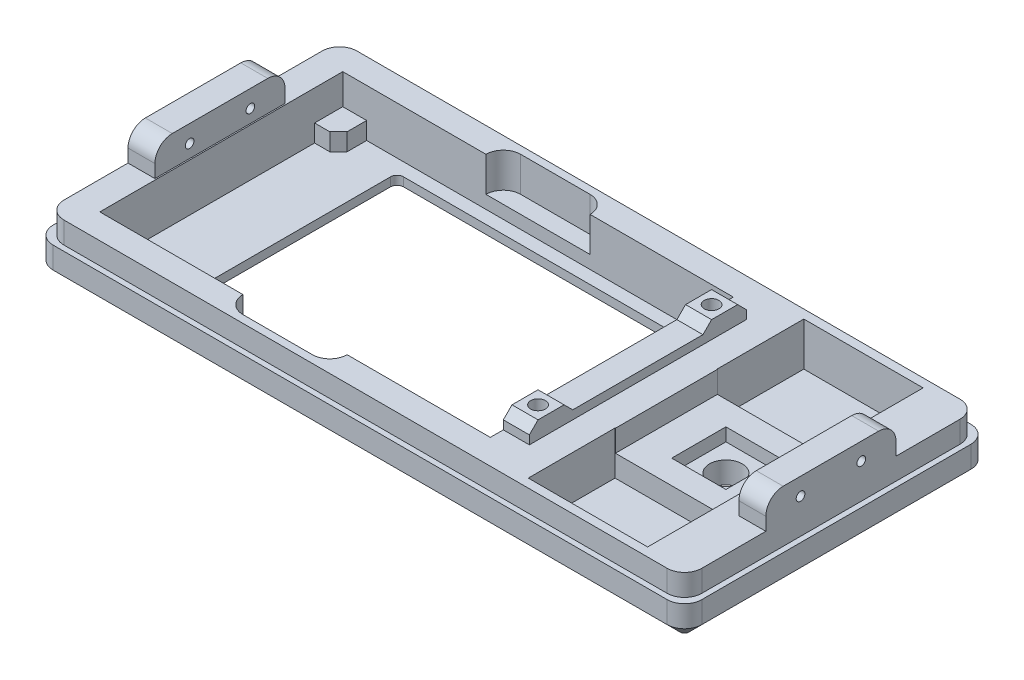
SolidWorks part; units mm, degrees
ref_plane "Front Plane" through (0, 0, 0) normal (0, 0, 1) x (1, 0, 0)
ref_plane "Top Plane" through (0, 0, 0) normal (0, 1, 0) x (1, 0, 0)
ref_plane "Right Plane" through (0, 0, 0) normal (1, 0, 0) x (0, 0, -1)
sketch "Sketch1" plane through (0, 0, 0) normal (0, 1, 0) x (1, 0, 0)
  line L1 (-74.75, 35) -> (74.75, 35)
  line L2 (-74.75, 35) -> (-74.75, -35)
  line L3 (-74.75, -35) -> (74.75, -35)
  line L4 (74.75, 35) -> (74.75, -35)
  line L5 (-74.75, 35) -> (74.75, -35) construction
  line L6 (-74.75, -35) -> (74.75, 35) construction
  point P0 (0, 0)
  dimension "D1" = 70
  dimension "D2" = 149.5
extrude "Boss-Extrude1" add sketch "Sketch1" along normal blind 8
fillet "Fillet1" radius 4 4 edges at (-74.75, 4, -35) (-74.75, 4, 35) (74.75, 4, -35) (74.75, 4, 35)
sketch "Sketch6" plane through (0, 8, 0) normal (0, 1, 0) x (1, 0, 0)
  line L1 (-73.5, 33.75) -> (73.5, 33.75)
  line L2 (-73.5, 33.75) -> (-73.5, -33.75)
  line L3 (-73.5, -33.75) -> (73.5, -33.75)
  line L4 (73.5, 33.75) -> (73.5, -33.75)
  line L5 (-73.5, 33.75) -> (73.5, -33.75) construction
  line L6 (-73.5, -33.75) -> (73.5, 33.75) construction
  point P0 (0, 0)
  dimension "D1" = 67.5
  dimension "D2" = 147
extrude "Boss-Extrude3" add sketch "Sketch6" along normal blind 5
fillet "Fillet2" radius 4 4 edges at (-73.5, 10.5, 33.75) (73.5, 10.5, 33.75) (73.5, 10.5, -33.75) (-73.5, 10.5, -33.75)
sketch "Sketch7" plane through (0, 13, 0) normal (0, 1, 0) x (1, 0, 0)
  line L0 (-73.5, 0) -> (0, 0) construction
  line L1 (-73.5, 29.75) -> (-73.5, -29.75) construction
  line L2 (0, 0) -> (0, 33.75) construction
  line L3 (69.5, 33.75) -> (-69.5, 33.75) construction
  line L4 (-73.5, -15) -> (-73.5, 15)
  line L5 (-73.5, 29.75) -> (-73.5, -29.75) construction
  line L6 (-73.5, 15) -> (-67.2945, 15)
  line L7 (-67.2945, 15) -> (-67.2945, -15)
  line L8 (-73.5, -15) -> (-67.2945, -15)
  line L9 (73.5, 15) -> (67.2945, 15)
  line L10 (73.5, -15) -> (73.5, 15)
  line L11 (73.5, -15) -> (67.2945, -15)
  line L12 (67.2945, 15) -> (67.2945, -15)
  point P14 (-67.2945, 0)
  dimension "D1" = 15
extrude "Boss-Extrude4" add sketch "Sketch7" along normal blind 7
sketch "Sketch8" plane through (-73.5, 0, 0) normal (-1, 0, 0) x (0, 0, 1)
  line L0 (0, 20) -> (0, 0) construction
  line L1 (-15, 20) -> (15, 20) construction
  circle A0 centre (-7, 16) radius 1
  circle A1 centre (7, 16) radius 1
  dimension "D1" = 2
  dimension "D2" = 4
  dimension "D3" = 14
extrude "Cut-Extrude3" cut sketch "Sketch8" against normal through all
fillet "Fillet5" radius 4 4 edges at (70.3973, 20, 15) (70.3973, 20, -15) (-70.3973, 20, 15) (-70.3973, 20, -15)
sketch "Sketch9" plane through (0, 13, 0) normal (0, 1, 0) x (1, 0, 0)
  line L0 (0, 0) -> (-67.2945, 0) construction
  line L1 (-67.2945, -15) -> (-67.2945, 15) construction
  line L3 (-67, 28) -> (23, 28)
  line L4 (-67, 28) -> (-67, -28)
  line L5 (-67, -28) -> (23, -28)
  line L6 (23, 28) -> (23, -28)
  line L7 (-67, 28) -> (23, -28) construction
  line L8 (-67, -28) -> (23, 28) construction
  point P5 (-22, 0)
  dimension "D1" = 90
  dimension "D2" = 56
  dimension "D3" = 22
extrude "Cut-Extrude4" cut sketch "Sketch9" against normal blind 7
sketch "Sketch10" plane through (0, 6, 0) normal (0, 1, 0) x (1, 0, 0)
  line L0 (-67, 28) -> (23, -28) construction
  line L1 (23, 28) -> (-67, -28) construction
  line L3 (-61.5, 28) -> (17.5, 28)
  line L4 (-61.5, 28) -> (-61.5, -28)
  line L5 (-61.5, -28) -> (17.5, -28)
  line L6 (17.5, 28) -> (17.5, -28)
  line L7 (-61.5, 28) -> (17.5, -28) construction
  line L8 (-61.5, -28) -> (17.5, 28) construction
  point P8 (-22, 0)
  dimension "D1" = 79
  dimension "D2" = 56
extrude "Cut-Extrude5" cut sketch "Sketch10" against normal blind 4
sketch "Sketch11" plane through (0, 2, 0) normal (0, 1, 0) x (1, 0, 0)
  line L0 (-61.5, 0) -> (17.5, 0) construction
  line L1 (-61.5, 28) -> (-61.5, -28) construction
  line L2 (17.5, -28) -> (17.5, 28) construction
  line L4 (-51.5, 25) -> (14.5, 25)
  line L5 (-51.5, 25) -> (-51.5, -25)
  line L6 (-51.5, -25) -> (14.5, -25)
  line L7 (14.5, 25) -> (14.5, -25)
  line L8 (-51.5, 25) -> (14.5, -25) construction
  line L9 (-51.5, -25) -> (14.5, 25) construction
  point P6 (-18.5, 0)
  dimension "D1" = 66
  dimension "D2" = 50
  dimension "D3" = 3
extrude "Cut-Extrude6" cut sketch "Sketch11" against normal through all
sketch "Sketch13" plane through (0, 13, 0) normal (0, 1, 0) x (1, 0, 0)
  line L0 (23, 0) -> (67.2945, 0) construction
  line L1 (23, -28) -> (23, 28) construction
  line L2 (67.2945, 11) -> (67.2945, -11) construction
  line L3 (23, -25) -> (23, 25)
  line L4 (23, 25) -> (29, 25)
  line L5 (29, 25) -> (29, -25)
  line L6 (23, -25) -> (29, -25)
  point P10 (29, 0)
  dimension "D1" = 25
  dimension "D2" = 6
extrude "Boss-Extrude5" add sketch "Sketch13" along normal blind 4
sketch "Sketch14" plane through (0, 17, 0) normal (0, 1, 0) x (1, 0, 0)
  line L0 (23, 0) -> (29, 0) construction
  line L1 (23, 25) -> (23, -25) construction
  line L2 (29, -25) -> (29, 25) construction
  circle A0 centre (26, 20) radius 1.6928
  circle A1 centre (26, -20) radius 1.6928
  dimension "D1" = 3
  dimension "D2" = 20
extrude "Cut-Extrude7" cut sketch "Sketch14" against normal through all
sketch "Sketch15" plane through (0, 17, 0) normal (0, 1, 0) x (1, 0, 0)
  line L0 (23, 0) -> (29, 0) construction
  line L1 (23, 25) -> (23, -25) construction
  line L2 (29, -25) -> (29, 25) construction
  line L3 (23, -15) -> (23, 15)
  line L4 (23, -28) -> (23, 28) construction
  line L5 (23, 15) -> (29, 15)
  line L6 (29, -25) -> (29, 25) construction
  line L7 (29, 15) -> (29, -15)
  line L8 (23, -15) -> (29, -15)
  dimension "D1" = 15
extrude "Cut-Extrude8" cut sketch "Sketch15" against normal blind 2
chamfer "Chamfer2" distance 2 angle 45 2 edges at (26, 0, 18.3072) (26, 0, -18.3072)
sketch "Sketch16" plane through (0, 13, 0) normal (0, 1, 0) x (1, 0, 0)
  line L0 (0, 0) -> (67.2945, 0) construction
  line L1 (67.2945, 11) -> (67.2945, -11) construction
  circle A0 centre (49.2945, 0) radius 3.75
  dimension "D1" = 7.5
  dimension "D2" = 18
extrude "Cut-Extrude9" cut sketch "Sketch16" against normal through all
sketch "Sketch17" plane through (0, 13, 0) normal (0, 1, 0) x (1, 0, 0)
  line L1 (43.0445, 6.25) -> (55.5445, 6.25)
  line L2 (43.0445, 6.25) -> (43.0445, -6.25)
  line L3 (43.0445, -6.25) -> (55.5445, -6.25)
  line L4 (55.5445, 6.25) -> (55.5445, -6.25)
  line L5 (43.0445, 6.25) -> (55.5445, -6.25) construction
  line L6 (43.0445, -6.25) -> (55.5445, 6.25) construction
  point P0 (49.2945, 0)
  dimension "D1" = 12.5
  dimension "D2" = 12.5
extrude "Cut-Extrude10" cut sketch "Sketch17" against normal blind 8
sketch "Sketch20" plane through (0, 13, 0) normal (0, 1, 0) x (1, 0, 0)
  line L0 (-67.2945, 0) -> (67.2945, 0) construction
  line L1 (-67.2945, -11) -> (-67.2945, 11) construction
  line L2 (67.2945, 11) -> (67.2945, -11) construction
  line L3 (-22, 28) -> (-22, 33.75) construction
  line L4 (23, 28) -> (-67, 28) construction
  line L5 (69.5, 33.75) -> (-69.5, 33.75) construction
  line L6 (-10, 28) -> (-34, 28)
  line L7 (-34, 28) -> (-34, 32)
  line L8 (-34, 32) -> (-10, 32)
  line L9 (-10, 28) -> (-10, 32)
  line L10 (-10, -28) -> (-10, -32)
  line L11 (-34, -32) -> (-10, -32)
  line L12 (-34, -28) -> (-34, -32)
  line L13 (-10, -28) -> (-34, -28)
  point P17 (-22, 32)
  dimension "D1" = 12
  dimension "D2" = 4
extrude "Cut-Extrude12" cut sketch "Sketch20" against normal blind 8
fillet "Fillet6" radius 4 4 edges at (-34, 9, 32) (-10, 9, 32) (-10, 9, -32) (-34, 9, -32)
chamfer "Chamfer3" distance 2 angle 45 4 edges at (26, 17, 15) (26, 17, -15) (26, 17, -25) (26, 17, 25)
sketch "Sketch23" plane through (0, 6, 0) normal (0, 1, 0) x (1, 0, 0)
  line L0 (-61.5, 0) -> (-67, 0) construction
  line L1 (-61.5, 28) -> (-61.5, -28) construction
  line L2 (-67, 28) -> (-67, -28) construction
  line L3 (-61.5, -21.5) -> (-61.5, 21.5)
  line L4 (-61.5, 28) -> (-61.5, -28) construction
  line L5 (-61.5, 21.5) -> (-67, 21.5)
  line L6 (-67, 21.5) -> (-67, -21.5)
  line L7 (-61.5, -21.5) -> (-67, -21.5)
  line L8 (-22, -28) -> (-22, -10.1702) construction
  line L9 (-10, -28) -> (-34, -28) construction
  line L10 (17.5, 21.5) -> (23, 21.5)
  line L11 (17.5, -21.5) -> (17.5, 21.5)
  line L12 (17.5, -21.5) -> (23, -21.5)
  line L13 (23, 21.5) -> (23, -21.5)
  point P12 (-67, 0)
  dimension "D1" = 21.5
  dimension "D2" = 5.5
extrude "Cut-Extrude15" cut sketch "Sketch23" against normal blind 4
fillet "Fillet7" radius 1.5 4 edges at (14.5, 1, -25) (14.5, 1, 25) (-51.5, 1, 25) (-51.5, 1, -25)
chamfer "Chamfer6" distance 2 angle 45 4 edges at (-61.5, 4, 21.5) (-61.5, 4, -21.5) (17.5, 4, 21.5) (17.5, 4, -21.5)
sketch "Sketch26" plane through (0, 13, 0) normal (0, 1, 0) x (1, 0, 0)
  line L0 (-69.5, -33.75) -> (69.5, -33.75) construction
  line L1 (35.5, -11.75) -> (63, -11.75)
  line L2 (35.5, -11.75) -> (35.5, -31.75)
  line L3 (35.5, -31.75) -> (63, -31.75)
  line L4 (63, -11.75) -> (63, -31.75)
  line L5 (35.5, -11.75) -> (63, -31.75) construction
  line L6 (35.5, -31.75) -> (63, -11.75) construction
  line L7 (73.5, -29.75) -> (73.5, -15) construction
  line L8 (0, 0) -> (16.2431, 0) construction
  line L9 (35.5, 31.75) -> (63, 31.75)
  line L10 (63, 11.75) -> (63, 31.75)
  line L11 (35.5, 11.75) -> (63, 11.75)
  line L12 (35.5, 11.75) -> (35.5, 31.75)
  point P0 (49.25, -21.75)
  dimension "D1" = 20
  dimension "D2" = 27.5
  dimension "D3" = 12
  dimension "D4" = 10.5
extrude "Cut-Extrude16" cut sketch "Sketch26" against normal blind 10
sketch "Sketch27" plane through (0, 13, 0) normal (0, 1, 0) x (1, 0, 0)
  line L0 (63, -31.75) -> (63, -11.75) construction
  line L1 (35.5891, 14.4188) -> (63, 14.4188)
  line L2 (35.5891, 14.4188) -> (35.5891, -14.4188)
  line L3 (35.5891, -14.4188) -> (63, -14.4188)
  line L4 (63, 14.4188) -> (63, -14.4188)
  line L5 (35.5891, 14.4188) -> (63, -14.4188) construction
  line L6 (35.5891, -14.4188) -> (63, 14.4188) construction
  point P0 (49.2945, 0)
extrude "Cut-Extrude17" cut sketch "Sketch27" against normal blind 5
chamfer "Chamfer7" distance 3 angle 45 8 edges at (0, 0, 35) (73.5784, 0, 33.8284) (-73.5784, 0, 33.8284) (74.75, 0, 0) (-74.75, 0, 0) (73.5784, 0, -33.8284) (-73.5784, 0, -33.8284) (0, 0, -35)
